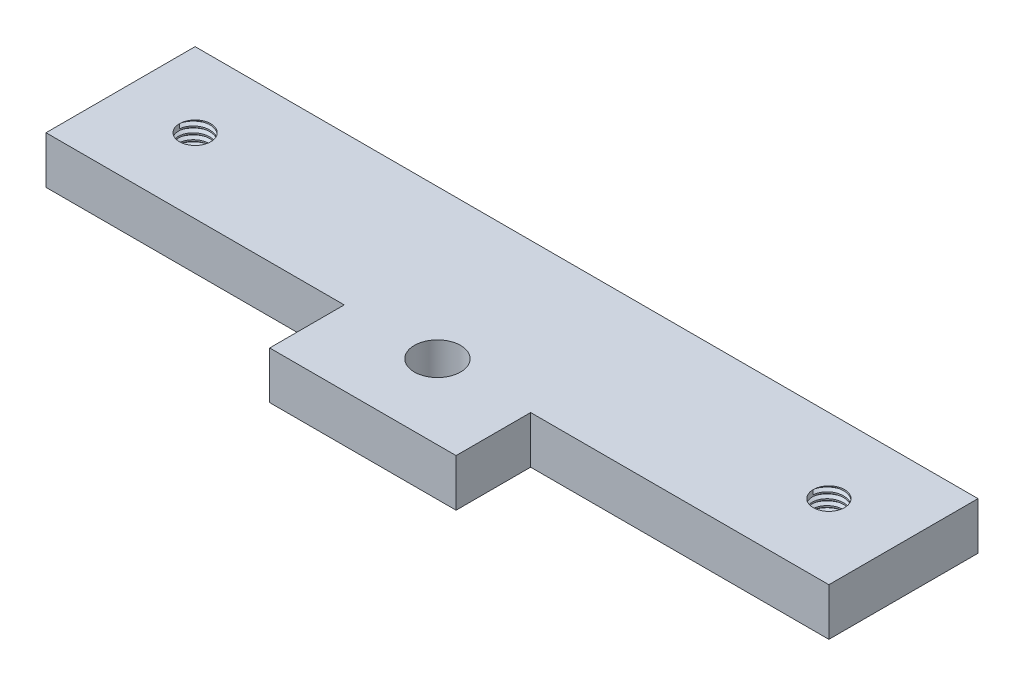
SolidWorks part; units mm, degrees
material "1060 Alloy"
ref_plane "Front Plane" through (0, 0, 0) normal (0, 0, 1) x (1, 0, 0)
ref_plane "Top Plane" through (0, 0, 0) normal (0, 1, 0) x (1, 0, 0)
ref_plane "Right Plane" through (0, 0, 0) normal (1, 0, 0) x (0, 0, -1)
sketch "Sketch1" plane through (0, 0, 0) normal (0, 1, 0) x (1, 0, 0)
  line L1 (-12.5, 0) -> (12.5, 0) construction
  line L2 (-12.5, 0) -> (-12.5, -10)
  line L3 (-12.5, -10) -> (12.5, -10)
  line L4 (12.5, 0) -> (12.5, -10)
  line L5 (-12.5, 0) -> (12.5, -10) construction
  line L6 (-12.5, -10) -> (12.5, 0) construction
  line L11 (0, 3.1) -> (0, 0) construction
  line L12 (0, 0) -> (0, -5) construction
  line L18 (12.5, 0) -> (52.5, 0)
  line L19 (52.5, 0) -> (52.5, 20)
  line L20 (52.5, 20) -> (-52.5, 20)
  line L21 (-52.5, 20) -> (-52.5, 0)
  line L22 (-52.5, 0) -> (-12.5, 0)
  line L24 (0, 0) -> (0, 20) construction
  line L25 (42.5, 10) -> (-42.5, 10) construction
  circle A0 centre (0, 0) radius 3.1
  circle A3 centre (42.5, 10) radius 2.1
  circle A4 centre (-42.5, 10) radius 2.1
  point P16 (0, -5)
  point P20 (0, 10)
  dimension "D1" = 6.2
  dimension "D5" = 4.2
  dimension "D7" = 4.2
  dimension "D2" = 25
  dimension "D3" = 10
  dimension "D6" = 5
  dimension "D8" = 10
  dimension "D9" = 10
  dimension "D10" = 10
  dimension "D11" = 85
extrude "Boss-Extrude1" add sketch "Sketch1" along normal blind 3.175 and the other way blind 3.175
thread "Thread1" pitch 0.8 method cut profile "Thread Profile1" start angle 0, offset 0, length 10, pitch 0.8, diameter 4.2
ref_plane "Plane1" through (-44.6, 3.175, -10) normal (0, 0, 1) x (-1, 0, 0)
sketch "Thread Profile1" plane through (-44.6, 3.175, -10) normal (0, 0, 1) x (-1, 0, 0)
  line L0 (0, 0) -> (0, 0.8) construction
  line L1 (0, 0) -> (0.433, 0.25)
  line L2 (0.433, 0.25) -> (0.433, 0.35)
  line L3 (0.433, 0.35) -> (0, 0.6)
  line L4 (0.433, 0.3) -> (0, 0.3) construction
  line L11 (0, 0) -> (0, 0.6)
  point P2 (0, 0)
  dimension "Pitch" = 0.8
  dimension "Profile_Angle" = 60
  dimension "Profile_Land" = 0.1
  dimension "Profile_Height" = 0.433
thread "Thread2" pitch 0.8 method cut profile "Thread Profile2" start angle 0, offset 0, length 10, pitch 0.8, diameter 4.2
ref_plane "Plane2" through (40.4, 3.175, -10) normal (0, 0, 1) x (-1, 0, 0)
sketch "Thread Profile2" plane through (40.4, 3.175, -10) normal (0, 0, 1) x (-1, 0, 0)
  line L0 (0, 0) -> (0, 0.8) construction
  line L1 (0, 0) -> (0.433, 0.25)
  line L2 (0.433, 0.25) -> (0.433, 0.35)
  line L3 (0.433, 0.35) -> (0, 0.6)
  line L4 (0.433, 0.3) -> (0, 0.3) construction
  line L11 (0, 0) -> (0, 0.6)
  point P2 (0, 0)
  dimension "Pitch" = 0.8
  dimension "Profile_Angle" = 60
  dimension "Profile_Land" = 0.1
  dimension "Profile_Height" = 0.433
